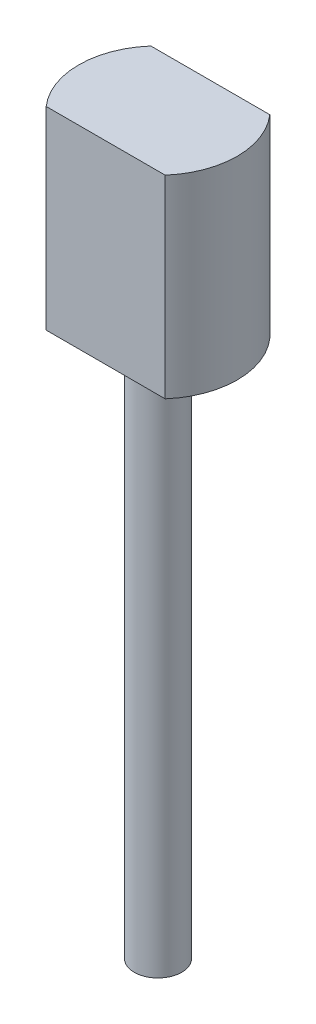
SolidWorks part; units mm, degrees
ref_plane "Front Plane" through (0, 0, 0) normal (0, 0, 1) x (1, 0, 0)
ref_plane "Top Plane" through (0, 0, 0) normal (0, 1, 0) x (1, 0, 0)
ref_plane "Right Plane" through (0, 0, 0) normal (1, 0, 0) x (0, 0, -1)
sketch "Sketch1" plane through (0, 0, 0) normal (0, 1, 0) x (1, 0, 0)
  circle A0 centre (0, 0) radius 3.4798
  dimension "D1" = 6.9596
extrude "Boss-Extrude1" add sketch "Sketch1" along normal blind 8.509
sketch "Sketch2" plane through (0, 0, 0) normal (0, -1, 0) x (1, 0, 0)
  circle A0 centre (0, 0) radius 1.0414
  dimension "D1" = 2.0828
extrude "Boss-Extrude2" add sketch "Sketch2" along normal blind 23.749
sketch "Sketch3" plane through (0, 8.509, 0) normal (0, 1, 0) x (1, 0, 0)
  line L0 (-2.6125, 2.2987) -> (2.6125, 2.2987)
  line L1 (-2.6125, -2.2987) -> (2.6125, -2.2987)
  line L2 (-3.4798, 0) -> (3.4798, 0) construction
  circle A0 centre (0, 0) radius 3.4798 construction
  arc A1 (2.6125, -2.2987) -> (2.6125, 2.2987) centre (0, 0) ccw
  arc A2 (-2.6125, 2.2987) -> (-2.6125, -2.2987) centre (0, 0) ccw
  dimension "D1" = 4.5974
extrude "Cut-Extrude1" cut sketch "Sketch3" against normal up to surface (8.509 mm away) flip side to cut up to face at (0, 0, 3.4798)
